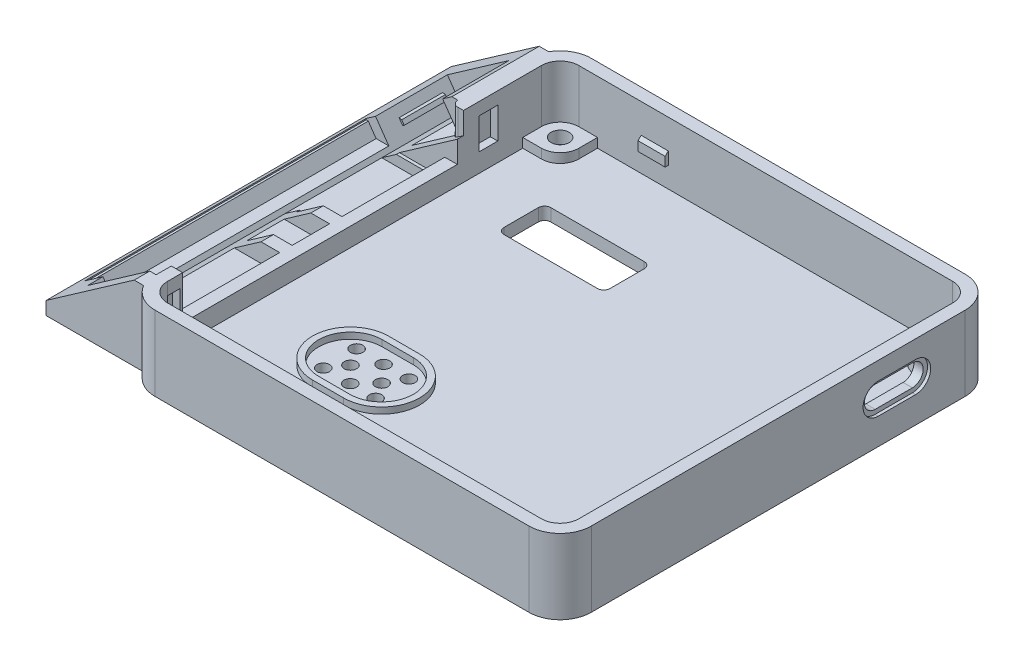
SolidWorks part; units mm, degrees
ref_plane "前视基准面" through (0, 0, 0) normal (0, 0, 1) x (1, 0, 0)
ref_plane "上视基准面" through (0, 0, 0) normal (0, 1, 0) x (1, 0, 0)
ref_plane "右视基准面" through (0, 0, 0) normal (1, 0, 0) x (0, 0, -1)
other "Configuration Table"
sketch "草图1" plane through (0, 0, 0) normal (0, 1, 0) x (1, 0, 0)
  line L1 (-30, -35) -> (30, -35)
  line L2 (-35, -30) -> (-35, 30)
  line L3 (-30, 35) -> (30, 35)
  line L4 (35, -30) -> (35, 30)
  line L5 (-35, -35) -> (35, 35) construction
  line L6 (-35, 35) -> (35, -35) construction
  line L7 (-30, -30) -> (30, -30) construction
  line L8 (-30, -30) -> (-30, 30) construction
  line L9 (-30, 30) -> (30, 30) construction
  line L10 (30, -30) -> (30, 30) construction
  line L11 (-30, -30) -> (30, 30) construction
  line L12 (-30, 30) -> (30, -30) construction
  arc A0 (-30, 35) -> (-35, 30) centre (-30, 30) ccw
  arc A1 (35, 30) -> (30, 35) centre (30, 30) ccw
  arc A2 (30, -35) -> (35, -30) centre (30, -30) ccw
  arc A3 (-35, -30) -> (-30, -35) centre (-30, -30) ccw
  point P0 (0, 0)
  point P6 (0, 0)
  dimension "D1" = 70
  dimension "D2" = 70
  dimension "D3" = 60
extrude "凸台-拉伸1" add sketch "草图1" along normal blind 2
sketch "草图2" plane through (0, 2, 0) normal (0, 1, 0) x (1, 0, 0)
  line L0 (-30, -35) -> (30, -35) construction
  line L1 (-35, 30) -> (-35, -30) construction
  line L2 (30, 35) -> (-30, 35) construction
  line L3 (35, -30) -> (35, 30) construction
  line L4 (-30, -35) -> (30, -35)
  line L5 (-35, 30) -> (-35, -30)
  line L6 (30, 35) -> (-30, 35)
  line L7 (35, -30) -> (35, 30)
  line L8 (-33, -30) -> (-33, 30)
  line L9 (-33, -33) -> (33, -33) construction
  line L10 (-33, -33) -> (-33, 33) construction
  line L11 (-33, 33) -> (33, 33) construction
  line L12 (33, -33) -> (33, 33) construction
  line L13 (-33, -33) -> (33, 33) construction
  line L14 (-33, 33) -> (33, -33) construction
  line L15 (-30, 33) -> (30, 33)
  line L16 (33, 30) -> (33, -30)
  line L17 (30, -33) -> (-30, -33)
  arc A0 (30, -35) -> (35, -30) centre (30, -30) ccw construction
  arc A1 (-35, -30) -> (-30, -35) centre (-30, -30) ccw construction
  arc A2 (-30, 35) -> (-35, 30) centre (-30, 30) ccw construction
  arc A3 (35, 30) -> (30, 35) centre (30, 30) ccw construction
  arc A4 (30, -35) -> (35, -30) centre (30, -30) ccw
  arc A5 (-35, -30) -> (-30, -35) centre (-30, -30) ccw
  arc A6 (-30, 35) -> (-35, 30) centre (-30, 30) ccw
  arc A7 (35, 30) -> (30, 35) centre (30, 30) ccw
  arc A8 (-33, 30) -> (-30, 33) centre (-30, 30) cw
  arc A9 (30, 33) -> (33, 30) centre (30, 30) cw
  arc A10 (33, -30) -> (30, -33) centre (30, -30) cw
  arc A11 (-30, -33) -> (-33, -30) centre (-30, -30) cw
  point P12 (0, 0)
  dimension "D1" = 2
extrude "凸台-拉伸2" add sketch "草图2" along normal blind 10
sketch "草图3" plane through (0, 12, 0) normal (0, 1, 0) x (1, 0, 0)
  line L1 (-33, -30) -> (-35, -30)
  line L2 (-33, -30) -> (-33, 30)
  line L3 (-33, 30) -> (-35, 30)
  line L4 (-35, -30) -> (-35, 30)
extrude "切除-拉伸1" cut sketch "草图3" against normal blind 7
sketch "草图4" plane through (0, 2, 0) normal (0, 1, 0) x (1, 0, 0)
  line L0 (-27, 30) -> (-27, 33)
  line L1 (30, 33) -> (-30, 33) construction
  line L2 (-27, 33) -> (-30, 33)
  line L3 (-30, 27) -> (-33, 27)
  line L4 (-33, -30) -> (-33, 30) construction
  line L5 (-33, 27) -> (-33, 30)
  line L6 (27, 30) -> (27, 33)
  line L7 (27, 33) -> (30, 33)
  line L8 (30, 27) -> (33, 27)
  line L9 (33, -30) -> (33, 30) construction
  line L10 (33, 27) -> (33, 30)
  line L11 (-33, -27) -> (-33, -30)
  line L12 (-30, -33) -> (30, -33) construction
  line L13 (-30, -33) -> (-27, -33)
  line L14 (33, -30) -> (33, -27)
  line L15 (-27, -30) -> (-27, -33)
  line L16 (-30, -27) -> (-33, -27)
  line L18 (33, -27) -> (30, -27)
  line L19 (27, -30) -> (27, -33)
  line L20 (27, -33) -> (30, -33)
  arc A0 (27, 30) -> (30, 27) centre (30, 30) ccw
  arc A1 (-30, 33) -> (-33, 30) centre (-30, 30) ccw
  arc A2 (-27, -30) -> (-30, -27) centre (-30, -30) ccw
  arc A4 (-30, 27) -> (-27, 30) centre (-30, 30) ccw
  arc A5 (33, 30) -> (30, 33) centre (30, 30) ccw
  arc A6 (-33, -30) -> (-30, -33) centre (-30, -30) ccw
  arc A7 (30, -33) -> (33, -30) centre (30, -30) ccw
  arc A8 (30, -27) -> (27, -30) centre (30, -30) ccw
extrude "凸台-拉伸3" add sketch "草图4" along normal blind 1.5
sketch "草图5" plane through (0, 3.5, 0) normal (0, 1, 0) x (1, 0, 0)
  circle A0 centre (30, -30) radius 1.45
  circle A1 centre (30, 30) radius 1.45
  circle A2 centre (-30, 30) radius 1.45
  circle A3 centre (-30, -30) radius 1.45
  dimension "D1" = 2.9
extrude "切除-拉伸2" cut sketch "草图5" against normal blind 2
sketch "草图6" plane through (0, 0, 0) normal (0, -1, 0) x (1, 0, 0)
  line L1 (-35, 30) -> (-50, 30)
  line L2 (-35, 30) -> (-35, -30)
  line L3 (-35, -30) -> (-50, -30)
  line L4 (-50, 30) -> (-50, -30)
  dimension "D1" = 15
extrude "凸台-拉伸4" add sketch "草图6" against normal blind 1
sketch "草图8" plane through (33, 0, 0) normal (-1, 0, 0) x (0, 0, 1)
  line L0 (-22.0249, 8.4152) -> (-16.0571, 8.4152)
  line L1 (-16.0571, 4.9395) -> (-22.0249, 4.9395)
  arc A0 (-16.0571, 8.4152) -> (-16.0571, 4.9395) centre (-16.0571, 6.6774) cw
  arc A1 (-22.0249, 4.9395) -> (-22.0249, 8.4152) centre (-22.0249, 6.6774) cw
extrude "切除-拉伸3" cut sketch "草图8" against normal blind 4
sketch "草图9" plane through (35, 0, 0) normal (1, 0, 0) x (0, 0, -1)
  line L0 (14.3193, 6.6774) -> (23.7628, 6.6774) construction
  line L1 (22.0249, 6.6774) -> (22.0249, 8.4152) construction
  line L2 (16.0571, 6.6774) -> (16.0571, 8.4152) construction
  line L3 (16.0571, 9.1152) -> (22.0249, 9.1152)
  line L4 (22.0249, 4.2395) -> (16.0571, 4.2395)
  line L5 (16.0571, 8.4152) -> (22.0249, 8.4152) construction
  arc A0 (16.0571, 8.4152) -> (16.0571, 4.9395) centre (16.0571, 6.6774) ccw construction
  arc A1 (22.0249, 4.9395) -> (22.0249, 8.4152) centre (22.0249, 6.6774) ccw construction
  arc A2 (22.0249, 9.1152) -> (22.0249, 4.2395) centre (22.0249, 6.6774) cw
  arc A3 (16.0571, 4.2395) -> (16.0571, 9.1152) centre (16.0571, 6.6774) cw
  dimension "D1" = 0.7
extrude "切除-拉伸4" cut sketch "草图9" against normal blind 0.5
sketch "草图10" plane through (0, 1, 0) normal (0, 1, 0) x (1, 0, 0)
  line L0 (-35, -30) -> (-50, -30) construction
  line L1 (-50, 30) -> (-48.7, 30)
  line L2 (-50, 30) -> (-50, -30)
  line L3 (-50, -30) -> (-48.7, -30)
  line L4 (-48.7, 30) -> (-48.7, -30)
  dimension "D1" = 1.3
extrude "凸台-拉伸5" add sketch "草图10" along normal blind 2
sketch "草图11" plane through (0, 0, 30) normal (0, 0, 1) x (1, 0, 0)
  line L0 (-43.7126, 1) -> (-38, 5)
  line L1 (-35, 1) -> (-48.7, 1) construction
  line L2 (-38, 5) -> (-35, 5)
  line L3 (-35, 5) -> (-35, 1)
  line L4 (-35, 1) -> (-43.7126, 1)
  line L5 (-48.7, 2.8) -> (-48.3604, 2.8)
  line L6 (-48.7, 3) -> (-48.7, 1) construction
  line L7 (-48.3604, 2.8) -> (-47.1, 1)
  line L8 (-47.1, 1) -> (-48.7, 1)
  line L9 (-48.7, 1) -> (-48.7, 2.8)
  dimension "D1" = 35
  dimension "D2" = 3
  dimension "D3" = 55
  dimension "D4" = 1.8
  dimension "D5" = 1.6
extrude "凸台-拉伸6" add sketch "草图11" against normal up to surface (60 mm away) up to face at (-44.5667, 1.3333, -30)
sketch "草图12" plane through (0, 0, 30) normal (0, 0, 1) x (1, 0, 0)
  line L0 (-45.0626, 1) -> (-44.6185, 0.3657)
  line L1 (-43.7126, 1) -> (-47.1, 1) construction
  line L2 (-44.6185, 0.3657) -> (-43.7126, 1)
  line L3 (-43.7126, 1) -> (-45.0626, 1)
  line L4 (-38, 5) -> (-43.7126, 1) construction
  dimension "D1" = 1.35
extrude "切除-拉伸5" cut sketch "草图12" against normal up to next and the other way through all
sketch "草图13" plane through (0, 5, 0) normal (0, 1, 0) x (1, 0, 0)
  line L0 (-35, 12) -> (-35, -30) construction
  line L1 (-44.6185, -30) -> (-44.6185, 30) construction
  line L2 (-35, -16) -> (-44.6185, -16)
  line L3 (-35, -16) -> (-35, -28)
  line L4 (-35, -28) -> (-44.6185, -28)
  line L5 (-44.6185, -16) -> (-44.6185, -28)
  line L6 (-35, -2) -> (-44.6185, -2)
  line L7 (-35, -2) -> (-35, -14)
  line L8 (-35, -14) -> (-44.6185, -14)
  line L9 (-44.6185, -2) -> (-44.6185, -14)
  line L11 (-35, 12) -> (-35, 0)
  line L12 (-35, 0) -> (-44.6185, 0)
  line L13 (-44.6185, 12) -> (-44.6185, 0)
  line L19 (-38, 30) -> (-44.6185, 30) construction
  line L20 (-35, 26) -> (-44.6185, 26) [skipped]
  line L21 (-44.6185, 26) -> (-44.6185, 14) [skipped]
  line L22 (-35, 26) -> (-35, 14) [skipped]
  line L23 (-35, 14) -> (-44.6185, 14) [skipped]
  line L24 (-44.6185, 28) -> (-35, 28)
  line L25 (-44.6185, 28) -> (-44.6185, 18.5)
  line L26 (-44.6185, 18.5) -> (-35, 18.5)
  line L27 (-35, 28) -> (-35, 18.5)
  line L28 (-38, -30) -> (-44.6185, -30) construction
  line L31 (-44.6185, 12) -> (-44.6185, 16.5)
  line L32 (-44.6185, 16.5) -> (-35, 16.5)
  line L33 (-35, 12) -> (-35, 16.5)
  line L34 (-35, 12) -> (-44.6185, 12) [skipped]
  dimension "D2" = 2
  dimension "D3" = 2
  dimension "D4" = 2
  dimension "D5" = 2
  dimension "D6" = 9.5
  dimension "D7" = 12
  dimension "D1" = 4
extrude "切除-拉伸6" cut sketch "草图13" against normal blind 3
sketch "草图14" plane through (-50, 0, 0) normal (-1, 0, 0) x (0, 0, 1)
  line L0 (-30, 12) -> (-35, 12) construction
  line L1 (-30, 0) -> (-32.5, 0)
  line L2 (-30, 0) -> (-30, 12)
  line L3 (-30, 12) -> (-32.5, 12)
  line L4 (-32.5, 0) -> (-32.5, 12)
  line L5 (35, 12) -> (30, 12) construction
  line L6 (30, 0) -> (32.5, 0)
  line L7 (30, 0) -> (30, 12)
  line L8 (30, 12) -> (32.5, 12)
  line L9 (32.5, 0) -> (32.5, 12)
extrude "凸台-拉伸7" add sketch "草图14" against normal blind 16
sketch "草图15" plane through (0, 0, 30) normal (0, 0, -1) x (-1, 0, 0)
  line L0 (35.8467, 12) -> (48.7, 3)
  line L1 (50, 12) -> (33, 12) construction
  line L2 (48.7, 3) -> (50, 3)
  line L3 (50, 3) -> (50, 12)
  line L4 (50, 12) -> (35.8467, 12)
  dimension "D1" = 145
extrude "切除-拉伸7" cut sketch "草图15" against normal mid plane 112
sketch "草图16" plane through (0, 0, -30) normal (0, 0, 1) x (1, 0, 0)
  line L0 (-50, 3) -> (-48.7, 3)
  line L1 (-48.7, 3) -> (-35.8467, 12)
  line L2 (-35.8467, 12) -> (-50, 12)
  line L3 (-50, 12) -> (-50, 3)
extrude "切除-拉伸8" cut sketch "草图16" against normal mid plane 18
sketch "草图17" plane through (0, 0, -32.5) normal (0, 0, -1) x (-1, 0, 0)
  line L0 (48.7, 3) -> (50, 2.0897)
  line L1 (50, 3) -> (50, 0) construction
  line L2 (50, 2.0897) -> (50, 3)
  line L3 (50, 3) -> (48.7, 3)
  line L4 (35.8467, 12) -> (48.7, 3) construction
extrude "切除-拉伸9" cut sketch "草图17" against normal up to next
sketch "草图18" plane through (-17.4313, 24.8945, 0) normal (-0.5736, 0.8192, 0) x (0.8192, 0.5736, 0)
  line L9 (-38.2526, -30.0551) -> (-34.6349, -30.0551)
  line L10 (-38.2526, -30.0551) -> (-38.2526, -27.5683)
  line L11 (-38.2526, -27.5683) -> (-34.6349, -27.5683)
  line L12 (-34.6349, -30.0551) -> (-34.6349, -27.5683)
  line L13 (-38.2526, 30.2595) -> (-24.2864, 30.2595)
  line L14 (-38.2526, 30.2595) -> (-38.2526, 29.1155)
  line L15 (-38.2526, 29.1155) -> (-24.2864, 29.1155)
  line L16 (-24.2864, 30.2595) -> (-24.2864, 29.1155)
extrude "凸台-拉伸11" add sketch "草图18" against normal up to surface (27.4873 mm away) up to face at (-33, 3.5, 0)
sketch "草图20" plane through (0, 5, 0) normal (0, 1, 0) x (1, 0, 0)
  line L0 (-33, 18.5) -> (-33, 17.5)
  line L1 (-33, 30) -> (-34.9, 30)
  line L2 (-33, 30) -> (-33, 18.5)
  line L4 (-34.9, 30) -> (-34.9, 18.4763)
  line L5 (-33, -30) -> (-34.8301, -30)
  line L6 (-33, -30) -> (-33, -27.5683)
  line L7 (-33, -27.5683) -> (-34.8301, -27.5683)
  line L8 (-34.8301, -30) -> (-34.8301, -27.5683)
  line L9 (-33, -30) -> (-33, 30) construction
  line L10 (-33, 17.5) -> (-33.9237, 17.5)
  arc A0 (-33.9237, 17.5) -> (-34.9, 18.4763) centre (-33.9237, 18.4763) cw
  dimension "D1" = 11.5
  dimension "D2" = 1.9
  dimension "D3" = 1
extrude "凸台-拉伸12" add sketch "草图20" along normal up to surface (7 mm away) up to face at (-7.0323, 12, 0)
sketch "草图21" plane through (0, 0, 32.5) normal (0, 0, 1) x (1, 0, 0)
  line L1 (-50, 0) -> (-18.8244, 0)
  line L2 (-50, 0) -> (-50, -21.4202)
  line L3 (-50, -21.4202) -> (-18.8244, -21.4202)
  line L4 (-18.8244, 0) -> (-18.8244, -21.4202)
extrude "切除-拉伸10" cut sketch "草图21" against normal up to surface (65 mm away) up to face at (-40.9014, 5.2179, -32.5)
sketch "草图22" plane through (-17.4313, 24.8945, 0) normal (-0.5736, 0.8192, 0) x (0.8192, 0.5736, 0)
  line L0 (-36.3395, -27.5683) -> (-36.3395, 29.1155) construction
  line L1 (-38.6019, 29.4194) -> (-36.3395, 29.4194)
  line L2 (-38.6019, 29.4194) -> (-38.6019, 17.5781)
  line L3 (-38.6019, 17.5781) -> (-36.3395, 17.5781)
  line L4 (-36.3395, 29.4194) -> (-36.3395, 17.5781)
extrude "凸台-拉伸14" add sketch "草图22" against normal up to surface (4.9454 mm away) up to face at (-9.7259, 0, 0)
sketch "草图23" plane through (0, 0, -16.5) normal (0, 0, 1) x (1, 0, 0)
  line L0 (-38, 5) -> (-33, 8.501)
  line L2 (-33, 8.501) -> (-33, 5)
  line L3 (-33, 5) -> (-38, 5)
  line L4 (-38, 5) -> (-42.2844, 2) construction
extrude "凸台-拉伸15" add sketch "草图23" against normal blind 2
sketch "草图24" plane through (-17.4313, 24.8945, 0) normal (-0.5736, 0.8192, 0) x (0.8192, 0.5736, 0)
  line L1 (-24.2864, 30) -> (-21.7055, 30)
  line L2 (-24.2864, 30) -> (-24.2864, 18.4763)
  line L3 (-24.2864, 18.4763) -> (-21.7055, 18.4763)
  line L4 (-21.7055, 30) -> (-21.7055, 18.4763)
extrude "凸台-拉伸16" add sketch "草图24" against normal up to surface (3.8555 mm away) up to face at (-33, 6.643, -0.9188)
sketch "草图25" plane through (0, 0, -35) normal (0, 0, -1) x (-1, 0, 0)
  line L0 (-30, 12) -> (30, 12) construction
  line L1 (29.1973, 12) -> (38.3709, 12)
  line L2 (29.1973, 12) -> (29.1973, 15.5813)
  line L3 (29.1973, 15.5813) -> (38.3709, 15.5813)
  line L4 (38.3709, 12) -> (38.3709, 15.5813)
extrude "切除-拉伸11" cut sketch "草图25" against normal blind 18
sketch "草图26" plane through (0, 0, -29.1155) normal (0, 0, 1) x (1, 0, 0)
  line L0 (-38, 5) -> (-34.9, 7.1706)
  line L1 (-34.9, 5) -> (-34.9, 7.5003) construction
  line L2 (-34.9, 7.1706) -> (-34.9, 5)
  line L3 (-34.9, 5) -> (-38, 5)
  line L4 (-38, 5) -> (-42.2844, 2) construction
extrude "凸台-拉伸17" add sketch "草图26" along normal up to surface (1.1155 mm away) up to face at (-37.5711, 3.5, -28)
sketch "草图27" plane through (33, 0, 0) normal (-1, 0, 0) x (0, 0, 1)
  line L0 (-39.7195, 10) -> (41.5559, 10) construction
  line L1 (30, 12) -> (-30, 12) construction
  line L2 (-39.7195, 5) -> (41.5559, 5) construction
  line L3 (30, 12) -> (30, 3.5) construction
  line L8 (-12.5, 10) -> (-9.5, 10)
  line L9 (-12.5, 10) -> (-12.5, 5)
  line L10 (-12.5, 5) -> (-9.5, 5)
  line L11 (-9.5, 10) -> (-9.5, 5)
  line L12 (4, 10) -> (7, 10)
  line L13 (4, 10) -> (4, 5)
  line L14 (4, 5) -> (7, 5)
  line L15 (7, 10) -> (7, 5)
  dimension "D1" = 2
  dimension "D2" = 5
  dimension "D3" = 3
  dimension "D4" = 3
  dimension "D5" = 13.5
  dimension "D6" = 23
extrude "切除-拉伸12" cut sketch "草图27" against normal blind 1.2
sketch "草图29" plane through (-33, 0, 0) normal (1, 0, 0) x (0, 0, -1)
  line L0 (-46.2025, 10) -> (42.2339, 10) construction
  line L1 (-46.2025, 5) -> (42.2339, 5) construction
  line L2 (17.5, 12) -> (30, 12) construction
  line L3 (30, 12) -> (30, 3.5) construction
  line L4 (20, 10) -> (23, 10)
  line L5 (20, 10) -> (20, 5)
  line L6 (20, 5) -> (23, 5)
  line L7 (23, 10) -> (23, 5)
  line L9 (-30, 10) -> (-28, 10)
  line L10 (-30, 10) -> (-30, 5)
  line L11 (-30, 5) -> (-28, 5)
  line L12 (-28, 10) -> (-28, 5)
  line L13 (-30, 12) -> (-30, 3.5) construction
  dimension "D1" = 2
  dimension "D2" = 5
  dimension "D3" = 3
  dimension "D4" = 7
  dimension "D5" = 2
extrude "切除-拉伸13" cut sketch "草图29" against normal blind 1.2
sketch "草图30" plane through (0, 2, 0) normal (0, 1, 0) x (1, 0, 0)
  line L0 (-44.6185, -27.5683) -> (-44.6185, 29.1155) construction
  line L1 (-37, 16) -> (-44.6185, 16)
  line L2 (-37, 16) -> (-37, 0.5)
  line L3 (-37, 0.5) -> (-44.6185, 0.5)
  line L4 (-44.6185, 16) -> (-44.6185, 0.5)
  line L5 (-33, 16.5) -> (-42.2844, 16.5) construction
  line L6 (-35, 0) -> (-35, 16.5) construction
  line L7 (-42.2844, 0) -> (-38, 0) construction
  dimension "D1" = 0.5
  dimension "D2" = 2
  dimension "D3" = 0.5
extrude "切除-拉伸14" cut sketch "草图30" against normal up to vertex (1.6343 mm away) up to point (-44.6185, 0.3657, 27.5683)
ref_plane "基准面1" through (0, 0, 8) normal (0, 0, 1) x (1, 0, 0)
sketch "草图31" plane through (0, 0, 8) normal (0, 0, 1) x (1, 0, 0)
  line L0 (-42.2844, 2) -> (-38, 5)
  line L1 (-38, 5) -> (-35, 5)
  line L2 (-35, 5) -> (-35, 2)
  line L3 (-35, 2) -> (-42.2844, 2)
extrude "凸台-拉伸18" add sketch "草图31" along normal blind 2
sketch "草图32" plane through (0, 0, 10) normal (0, 0, 1) x (1, 0, 0)
  line L0 (-38, 5) -> (-35, 5)
  line L1 (-35, 5) -> (-35, 2)
  line L2 (-35, 2) -> (-42.2844, 2)
  line L3 (-42.2844, 2) -> (-38, 5)
extrude "切除-拉伸15" cut sketch "草图32" along normal blind 7
sketch "草图33" plane through (0, 0, -33) normal (0, 0, 1) x (1, 0, 0)
  line L0 (-30, 12) -> (-30, 3.5) construction
  line L1 (-20, 7.3) -> (-15.6463, 7.3)
  line L2 (-20, 7.3) -> (-20, 5.3)
  line L3 (-20, 5.3) -> (-15.6463, 5.3)
  line L4 (-15.6463, 7.3) -> (-15.6463, 5.3)
  line L5 (30, 12) -> (-30, 12) construction
  dimension "D1" = 2
  dimension "D2" = 10
  dimension "D3" = 4.7
extrude "凸台-拉伸19" add sketch "草图33" along normal blind 0.5
chamfer "倒角1" distance 0.5 angle 45 1 edges at (-17.8231, 7.3, -32.5)
sketch "草图34" plane through (0, 0, 33) normal (0, 0, -1) x (-1, 0, 0)
  line L0 (30, 12) -> (30, 3.5) construction
  line L1 (14.2735, 7.3) -> (20, 7.3)
  line L2 (14.2735, 7.3) -> (14.2735, 5.3)
  line L3 (14.2735, 5.3) -> (20, 5.3)
  line L4 (20, 7.3) -> (20, 5.3)
  line L5 (30, 12) -> (-30, 12) construction
  dimension "D1" = 2
  dimension "D2" = 10
  dimension "D3" = 4.7
extrude "凸台-拉伸20" add sketch "草图34" along normal blind 0.5
chamfer "倒角2" distance 0.5 angle 45 1 edges at (-17.1368, 7.3, 32.5)
sketch "草图35" plane through (0, 2, 0) normal (0, 1, 0) x (1, 0, 0)
  line L0 (30, 33) -> (-30, 33) construction
  line L1 (-6.5, 21) -> (-23.5, 21)
  line L2 (-6.5, 21) -> (-6.5, 13.5)
  line L3 (-6.5, 13.5) -> (-23.5, 13.5)
  line L4 (-23.5, 21) -> (-23.5, 13.5)
  line L5 (-33, 17.5) -> (-33, 30) construction
  dimension "D1" = 7.5
  dimension "D2" = 17
  dimension "D3" = 12
  dimension "D4" = 9.5
extrude "切除-拉伸16" cut sketch "草图35" against normal up to surface (2 mm away) up to face at (-9.7259, 0, 0)
sketch "草图36" plane through (0, 2, 0) normal (0, 1, 0) x (1, 0, 0)
  line L0 (-16.6713, -16.9728) -> (-11.6713, -16.9728) construction
  line L1 (-16.6713, -11.8728) -> (-11.6713, -11.8728)
  line L2 (-16.6713, -22.0728) -> (-11.6713, -22.0728)
  line L3 (-16.6713, -16.9728) -> (-11.6713, -16.9728) construction
  line L4 (-16.6713, -10.8728) -> (-11.6713, -10.8728)
  line L5 (-16.6713, -23.0728) -> (-11.6713, -23.0728)
  arc A0 (-16.6713, -11.8728) -> (-16.6713, -22.0728) centre (-16.6713, -16.9728) ccw
  arc A1 (-11.6713, -22.0728) -> (-11.6713, -11.8728) centre (-11.6713, -16.9728) ccw
  arc A2 (-16.6713, -10.8728) -> (-16.6713, -23.0728) centre (-16.6713, -16.9728) ccw
  arc A3 (-11.6713, -23.0728) -> (-11.6713, -10.8728) centre (-11.6713, -16.9728) ccw
  point P2 (-14.1713, -16.9728)
  point P9 (-14.1713, -16.9728)
  dimension "D1" = 10.2
  dimension "D3" = 1
  dimension "D2" = 5
extrude "凸台-拉伸21" add sketch "草图36" along normal blind 1
sketch "草图37" plane through (0, 2, 0) normal (0, 1, 0) x (1, 0, 0)
  circle A0 centre (-11.6713, -16.9728) radius 1
  circle A1 centre (-16.6713, -16.9728) radius 1
  circle A2 centre (-14.1255, -14.2044) radius 1
  circle A3 centre (-18.4511, -14.2044) radius 1
  circle A4 centre (-10.0565, -14.2044) radius 1
  circle A5 centre (-18.4511, -19.5564) radius 1
  circle A6 centre (-14.1255, -19.5564) radius 1
  circle A7 centre (-10.0565, -19.5564) radius 1
  dimension "D1" = 2
extrude "切除-拉伸17" cut sketch "草图37" against normal up to surface (2 mm away) up to face at (-15, 0, -17.25)
fillet "圆角1" radius 1 4 edges at (-6.5, 1, -13.5) (-23.5, 1, -13.5) (-23.5, 1, -21) (-6.5, 1, -21)
sketch "草图38" plane through (-29.7676, -20.8435, 0) normal (0.8192, 0.5736, 0) x (0, 0, -1)
  line L0 (32.5, 19.691) -> (32.5, 28.6788) construction
  line L1 (20.5, 28.8906) -> (27.5, 28.8906)
  line L2 (20.5, 28.8906) -> (20.5, 27.8906)
  line L3 (20.5, 27.8906) -> (27.5, 27.8906)
  line L4 (27.5, 28.8906) -> (27.5, 27.8906)
  line L5 (17.5781, 30.3906) -> (29.1155, 30.3906) construction
  dimension "D1" = 1
  dimension "D2" = 7
  dimension "D3" = 5
  dimension "D4" = 1.5
extrude "凸台-拉伸22" add sketch "草图38" along normal blind 0.3
sketch "草图39" plane through (-19.8943, -13.9301, 0) normal (-0.8192, -0.5736, 0) x (0, 0, 1)
  line L0 (-32.5, 19.691) -> (-32.5, 29.5208) construction
  line L1 (-27.5, 28.8906) -> (-20.5, 28.8906)
  line L2 (-27.5, 28.8906) -> (-27.5, 27.8906)
  line L3 (-27.5, 27.8906) -> (-20.5, 27.8906)
  line L4 (-20.5, 28.8906) -> (-20.5, 27.8906)
  line L5 (-29.1155, 30.3906) -> (-18.4763, 30.3906) construction
  dimension "D1" = 1
  dimension "D2" = 5
  dimension "D3" = 7
  dimension "D4" = 1.5
extrude "凸台-拉伸23" add sketch "草图39" along normal blind 0.3
chamfer "倒角3" distance 0.3 angle 45 2 edges at (-36.711, 9.5636, -24) (-46.0928, 2.9944, -24)
